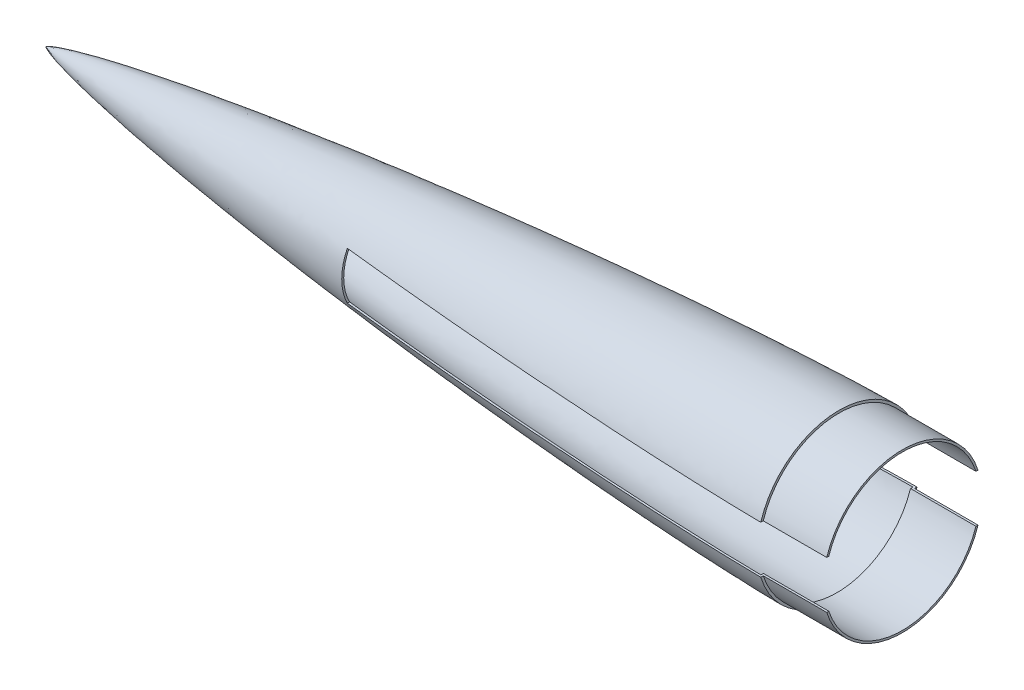
SolidWorks part; units mm, degrees
ref_plane "Front Plane" through (0, 0, 0) normal (0, 0, 1) x (1, 0, 0)
ref_plane "Top Plane" through (0, 0, 0) normal (0, 1, 0) x (1, 0, 0)
ref_plane "Right Plane" through (0, 0, 0) normal (1, 0, 0) x (0, 0, -1)
sketch "Sketch1" plane through (0, 0, 0) normal (0, 0, 1) x (1, 0, 0)
  line L0 (0, 0) -> (685.8, 0)
  line L1 (55.2447, 0) -> (-55.2447, 0) construction
  line L2 (685.8, 63.5) -> (635, 63.5)
  line L3 (635, 63.5) -> (635, 65.405)
  line L4 (685.8, 63.5) -> (685.8, 0)
  spline S0 degree 4 poles (0, 0) (0.0022, 0.0063) (0.0075, 0.0184) (0.0223, 0.0404) (0.057, 0.0804) (0.1098, 0.1304) (0.1816, 0.1889) (0.2836, 0.2634) (0.4063, 0.3444) (0.5502, 0.4318) (0.7155, 0.5251) (0.9567, 0.6537) (1.3318, 0.8391) (1.9703, 1.1275) (3.1158, 1.5922) (5.1634, 2.3284) (8.9332, 3.5155) (16.022, 5.4463) (28.2617, 8.305) (49.1788, 12.5136) (77.9573, 17.4873) (112.8708, 22.8061) (151.8575, 28.1242) (190.9036, 32.9827) (229.9952, 37.4592) (269.1232, 41.6038) (308.2821, 45.4454) (347.4678, 49.0026) (386.6776, 52.2836) (425.9094, 55.2895) (465.1619, 58.0128) (504.4341, 60.4362) (538.8141, 62.2665) (568.2945, 63.5925) (591.9899, 64.4666) (607.8766, 64.942) (620.8678, 65.2384) (628.9431, 65.3608) (632.981, 65.3999) (635, 65.405) knots 0 0 0 0 0 0.000041 0.000083 0.000165 0.000331 0.000496 0.000661 0.000955 0.001249 0.001549 0.001849 0.002664 0.003866 0.00593 0.009578 0.01627 0.028579 0.051871 0.088176 0.149698 0.211221 0.272743 0.334265 0.395788 0.45731 0.518832 0.580355 0.641877 0.703399 0.764922 0.826444 0.887966 0.918727 0.949489 0.974744 0.987372 1 1 1 1 1 construction
  spline S1 degree 4 poles (0, 0) (0.0022, 0.0063) (0.0075, 0.0184) (0.0223, 0.0404) (0.057, 0.0804) (0.1098, 0.1304) (0.1816, 0.1889) (0.2836, 0.2634) (0.4063, 0.3444) (0.5502, 0.4318) (0.7155, 0.5251) (0.9567, 0.6537) (1.3318, 0.8391) (1.9703, 1.1275) (3.1158, 1.5922) (5.1634, 2.3284) (8.9332, 3.5155) (16.022, 5.4463) (28.2617, 8.305) (49.1788, 12.5136) (77.9573, 17.4873) (112.8708, 22.8061) (151.8575, 28.1242) (190.9036, 32.9827) (229.9952, 37.4592) (269.1232, 41.6038) (308.2821, 45.4454) (347.4678, 49.0026) (386.6776, 52.2836) (425.9094, 55.2895) (465.1619, 58.0128) (504.4341, 60.4362) (538.8141, 62.2665) (568.2945, 63.5925) (591.9899, 64.4666) (607.8766, 64.942) (620.8678, 65.2384) (628.9431, 65.3608) (632.981, 65.3999) (635, 65.405) knots 0 0 0 0 0 0.000041 0.000083 0.000165 0.000331 0.000496 0.000661 0.000955 0.001249 0.001549 0.001849 0.002664 0.003866 0.00593 0.009578 0.01627 0.028579 0.051871 0.088176 0.149698 0.211221 0.272743 0.334265 0.395788 0.45731 0.518832 0.580355 0.641877 0.703399 0.764922 0.826444 0.887966 0.918727 0.949489 0.974744 0.987372 1 1 1 1 1
  dimension "D1" = 635
  dimension "D2" = 50.8
  dimension "D3" = 63.5
  dimension "D4" = 65.405
revolve "Revolve1" add sketch "Sketch1" angle 360 about L0
shell "Shell1" thickness 1.5875 removed face at (685.8, 0, 63.5)
sketch "Sketch2" plane through (685.8, 0, 0) normal (1, 0, 0) x (0, 0, -1)
  line L1 (-76.2, 19.05) -> (76.2, 19.05)
  line L2 (-76.2, 19.05) -> (-76.2, -19.05)
  line L3 (-76.2, -19.05) -> (76.2, -19.05)
  line L4 (76.2, 19.05) -> (76.2, -19.05)
  line L5 (-76.2, 19.05) -> (76.2, -19.05) construction
  line L6 (-76.2, -19.05) -> (76.2, 19.05) construction
  line L8 (-76.2, -18.415) -> (-76.2, 18.415)
  line L10 (76.2, -18.415) -> (76.2, 18.415)
  line L11 (-76.2, -18.415) -> (76.2, 18.415) construction
  line L12 (-76.2, 18.415) -> (76.2, -18.415) construction
  point P0 (0, 0)
  point P6 (0, 0)
  circle M3 centre (0, 0) radius 61.9125
  circle M4 centre (0, 0) radius 63.5
  dimension "D1" = 38.1
  dimension "D2" = 152.4
extrude "Cut-Extrude1" cut sketch "Sketch2" against normal blind 406.4 contours L3 L1 M3 | L4 L1 L3 M4 | L3 L1 M3 M4 | L2 L3 L1 M4 | L3 L1 M4 M3 region at (685.8, 0, 69.3395) region at (685.8, 18.6662, 59.742) region at (685.8, 0, 0) region at (685.8, 9.5784, -62.3852) region at (685.8, 0, -69.3395)
equation "\"D_o\"= 5.15in"
equation "\"D_i\"= 5in"
equation "\"D_c\"= 4.8in"
equation "\"L\"= 25in"
equation "\"L_s\"= 2in"
equation "\"D2@Sketch1\"=\"L_s\""
equation "\"D1@Sketch1\"=\"L\""
equation "\"D3@Sketch1\"=\"D_i\"/2"
equation "\"D4@Sketch1\"=\"D_o\"/2"
